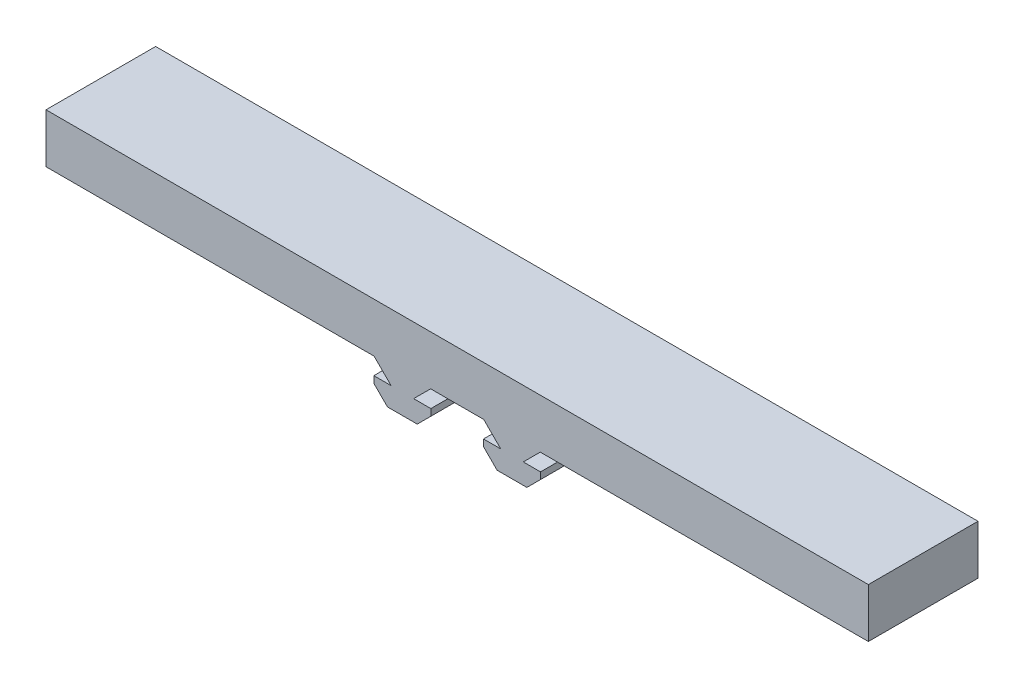
SolidWorks part; units mm, degrees
ref_plane "Front Plane" through (0, 0, 0) normal (0, 0, 1) x (1, 0, 0)
ref_plane "Top Plane" through (0, 0, 0) normal (0, 1, 0) x (1, 0, 0)
ref_plane "Right Plane" through (0, 0, 0) normal (1, 0, 0) x (0, 0, -1)
sketch "Sketch1" plane through (0, 0, 0) normal (0, 0, 1) x (1, 0, 0)
  line L0 (39.1271, 41.999) -> (40.9271, 40.199)
  line L1 (-21.2929, 51.999) -> (128.7071, 51.999)
  line L2 (-21.2929, 51.999) -> (-21.2929, 41.999)
  line L3 (-21.2929, 41.999) -> (39.1271, 41.999)
  line L4 (128.7071, 51.999) -> (128.7071, 41.999)
  line L5 (40.9271, 40.199) -> (38.2071, 40.199)
  line L6 (38.2071, 40.199) -> (38.2071, 38.559)
  line L7 (38.2071, 38.559) -> (40.8671, 35.899)
  line L8 (40.8671, 35.899) -> (46.5471, 35.899)
  line L9 (43.7071, 35.899) -> (43.7071, 41.999) construction
  line L10 (49.2071, 38.559) -> (46.5471, 35.899)
  line L11 (49.2071, 40.199) -> (49.2071, 38.559)
  line L12 (46.4871, 40.199) -> (49.2071, 40.199)
  line L13 (48.2871, 41.999) -> (46.4871, 40.199)
  line L14 (53.7071, 103.2482) -> (53.7071, 0.7497) construction
  line L15 (63.7071, 35.899) -> (63.7071, 41.999) construction
  line L16 (59.1271, 41.999) -> (60.9271, 40.199)
  line L17 (60.9271, 40.199) -> (58.2071, 40.199)
  line L18 (58.2071, 40.199) -> (58.2071, 38.559)
  line L19 (58.2071, 38.559) -> (60.8671, 35.899)
  line L20 (66.5471, 35.899) -> (60.8671, 35.899)
  line L21 (69.2071, 38.559) -> (66.5471, 35.899)
  line L22 (69.2071, 40.199) -> (69.2071, 38.559)
  line L23 (66.4871, 40.199) -> (69.2071, 40.199)
  line L24 (68.2871, 41.999) -> (66.4871, 40.199)
  line L25 (48.2871, 41.999) -> (59.1271, 41.999)
  line L26 (68.2871, 41.999) -> (128.7071, 41.999)
  point P31 (53.7071, 51.999)
  point P32 (-14.0729, 35.899)
  point P33 (-15.8729, 41.999)
  point P34 (-21.2929, 51.999)
  point P35 (-6.2737, 41.999)
  point P36 (0, 0)
  point P37 (-14.0729, 35.899)
  point P38 (-8.4529, 40.199)
  point P39 (-6.7129, 41.999)
  point P40 (-21.2929, 51.999)
  point P41 (-21.2929, 41.999)
  point P42 (48.4073, 51.999)
  dimension "D1" = 5.42
  dimension "D2" = 10
  dimension "D3" = 45
  dimension "D4" = 150
  dimension "D5" = 1.8
  dimension "D6" = 4.3
  dimension "D7" = 10
  dimension "D8" = 1.64
  dimension "D9" = 4.5
extrude "Boss-Extrude1" add sketch "Sketch1" along normal blind 20
other "Move Face1" flip direction yes face at (67.8471, 40.199, 10) face at (67.3871, 41.099, 10) face at (69.2071, 39.379, 10) face at (67.8771, 37.229, 10) face at (63.7071, 35.899, 10) face at (58.2071, 39.379, 10) face at (59.5671, 40.199, 10) face at (59.5371, 37.229, 10) face at (60.0271, 41.099, 10) face at (47.3871, 41.099, 10) face at (47.8471, 40.199, 10) face at (49.2071, 39.379, 10) face at (47.8771, 37.229, 10) face at (43.7071, 35.899, 10) face at (39.5371, 37.229, 10) face at (38.2071, 39.379, 10) face at (39.5671, 40.199, 10) face at (40.0271, 41.099, 10) offset 0.3 parameters "D1"=0.3
other "Move Face2" flip direction yes face at (53.7071, 41.999, 10) face at (9.1292, 41.999, 10) face at (98.285, 41.999, 10) offset 1 parameters "D1"=1
